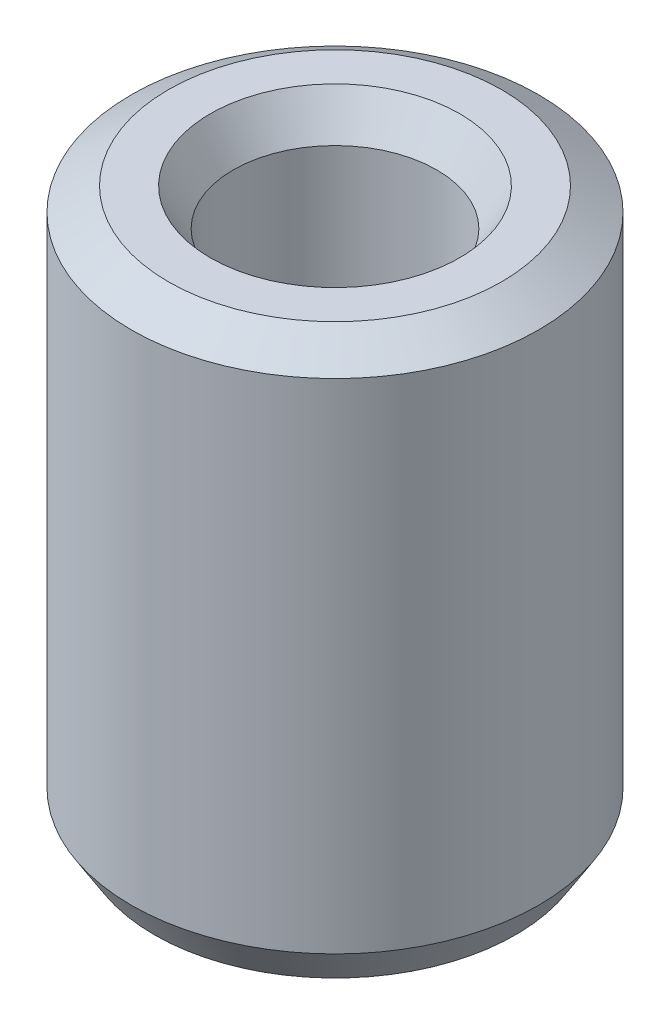
SolidWorks part; units mm, degrees
ref_plane "Front Plane" through (0, 0, 0) normal (0, 0, 1) x (1, 0, 0)
ref_plane "Top Plane" through (0, 0, 0) normal (0, 1, 0) x (1, 0, 0)
ref_plane "Right Plane" through (0, 0, 0) normal (1, 0, 0) x (0, 0, -1)
sketch "Sketch1" plane through (0, 0, 0) normal (0, 1, 0) x (1, 0, 0)
  circle A0 centre (0, 0) radius 7.5
  dimension "SLEEVE_OD" = 15
extrude "Boss-Extrude1" add sketch "Sketch1" along normal blind 20.5636
sketch "Sketch2" plane through (0, 0, 0) normal (0, 1, 0) x (1, 0, 0)
  circle A0 centre (0, 0) radius 3.7471
  dimension "BORE_D" = 7.4943
extrude "Cut-Extrude1" cut sketch "Sketch2" along normal through all
chamfer "Chamfer1" distance 0.8472 angle 58.225 4 edges at (0, 20.5636, 3.7471) (0, 0, 3.7471) (0, 0, 7.5) (0, 20.5636, 7.5) first distance on face at (0, 20.5636, 3.7471) first distance on face at (0, 0, 3.7471) first distance on face at (0, 20.5636, 7.5)
